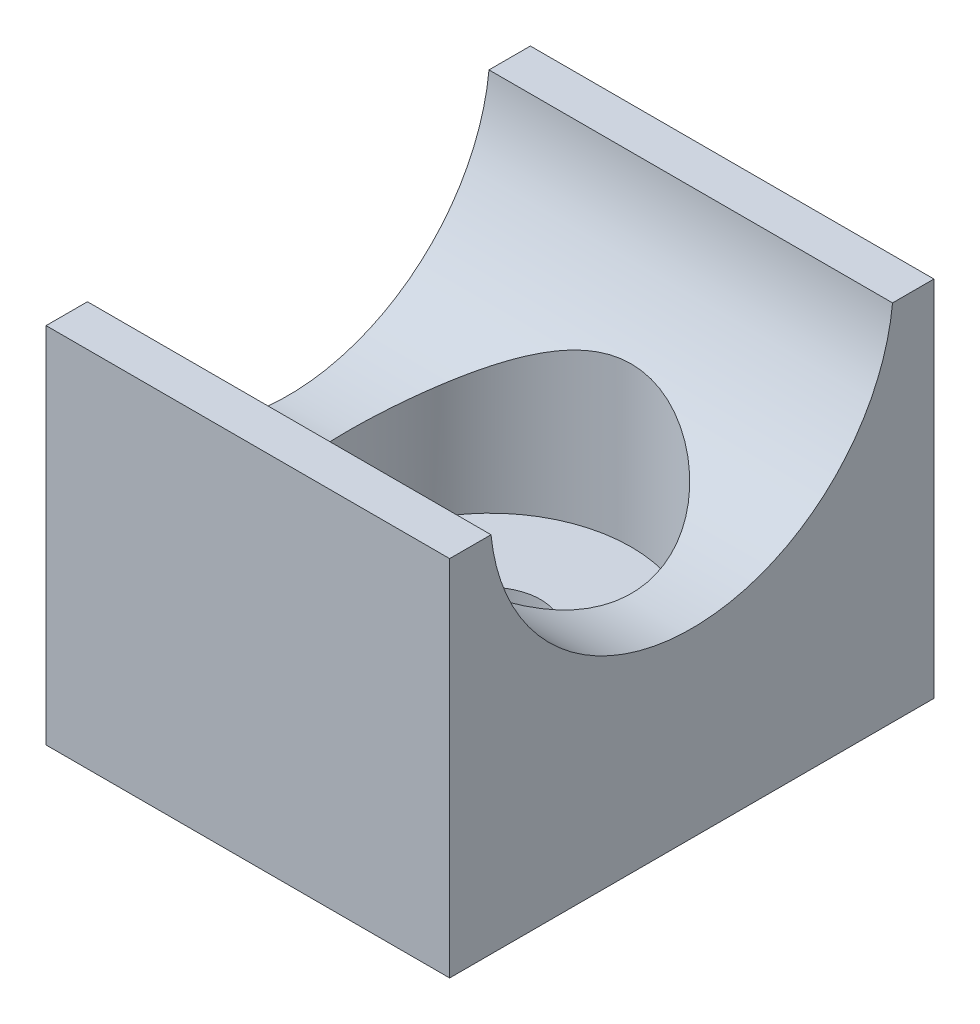
SolidWorks part; units mm, degrees
ref_plane "Front Plane" through (0, 0, 0) normal (0, 0, 1) x (1, 0, 0)
ref_plane "Top Plane" through (0, 0, 0) normal (0, 1, 0) x (1, 0, 0)
ref_plane "Right Plane" through (0, 0, 0) normal (1, 0, 0) x (0, 0, -1)
sketch "Sketch1" plane through (0, 0, 0) normal (1, 0, 0) x (0, 0, -1)
  line L0 (27.8763, 22.86) -> (30.48, 22.86)
  line L1 (0, 0) -> (30.48, 0)
  line L2 (0, 0) -> (0, 22.86)
  line L3 (0, 22.86) -> (2.6037, 22.86)
  line L4 (30.48, 0) -> (30.48, 22.86)
  arc A0 (2.6037, 22.86) -> (27.8763, 22.86) centre (15.24, 24.13) ccw
  dimension "D3" = 12.7
  dimension "D1" = 30.48
  dimension "D2" = 22.86
  dimension "D4" = 1.27
extrude "Boss-Extrude1" add sketch "Sketch1" along normal blind 25.4
sketch "Sketch2" plane through (0, 0, 0) normal (0, -1, 0) x (1, 0, 0)
  line L0 (12.7, 0) -> (12.7, -30.48) construction
  line L1 (25.4, 0) -> (0, 0) construction
  line L2 (25.4, -30.48) -> (0, -30.48) construction
  line L3 (25.4, -15.24) -> (0, -15.24) construction
  line L4 (25.4, 0) -> (25.4, -30.48) construction
  line L5 (0, 0) -> (0, -30.48) construction
  circle A0 centre (12.7, -15.24) radius 3.175
  point P14 (12.7, -15.24)
  dimension "D1" = 6.35
extrude "Cut-Extrude1" cut sketch "Sketch2" against normal through all and the other way through all
ref_plane "Plane1" through (0, 22.86, 0) normal (0, 1, 0) x (1, 0, 0)
sketch "Sketch3" plane through (0, 22.86, 0) normal (0, 1, 0) x (1, 0, 0)
  line L0 (0, 15.24) -> (25.4, 15.24) construction
  line L1 (0, 27.8763) -> (0, 2.6037) construction
  line L2 (25.4, 2.6037) -> (25.4, 27.8763) construction
  line L3 (12.7, 0) -> (12.7, 30.48) construction
  line L4 (25.4, 0) -> (0, 0) construction
  line L5 (25.4, 30.48) -> (0, 30.48) construction
  circle A0 centre (12.7, 15.24) radius 8.89
  dimension "D1" = 17.78
extrude "Cut-Extrude3" cut sketch "Sketch3" against normal offset from surface (17.78 mm away) 5.08 contours A0 up to face at (12.7, 0, -12.065)
